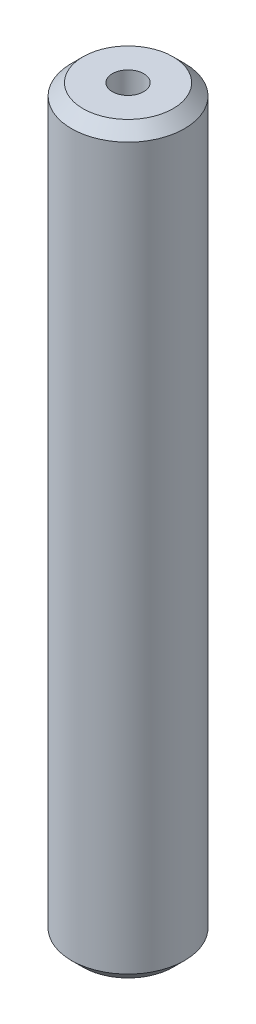
SolidWorks part; units mm, degrees
ref_plane "Front Plane" through (0, 0, 0) normal (0, 0, 1) x (1, 0, 0)
ref_plane "Top Plane" through (0, 0, 0) normal (0, 1, 0) x (1, 0, 0)
ref_plane "Right Plane" through (0, 0, 0) normal (1, 0, 0) x (0, 0, -1)
sketch "Sketch1" plane through (0, 0, 0) normal (0, 1, 0) x (1, 0, 0)
  circle A0 centre (0, 0) radius 12.5
  dimension "SHAFT_OD" = 25
extrude "Boss-Extrude1" add sketch "Sketch1" along normal blind 164.354
sketch "Sketch2" plane through (0, 0, 0) normal (0, 1, 0) x (1, 0, 0)
  circle A0 centre (0, 0) radius 3.4627
  dimension "BORE_D" = 6.9254
extrude "Cut-Extrude1" cut sketch "Sketch2" along normal through all
chamfer "Chamfer1" distance 2.5516 angle 45 2 edges at (0, 164.354, 12.5) (0, 0, 12.5)
